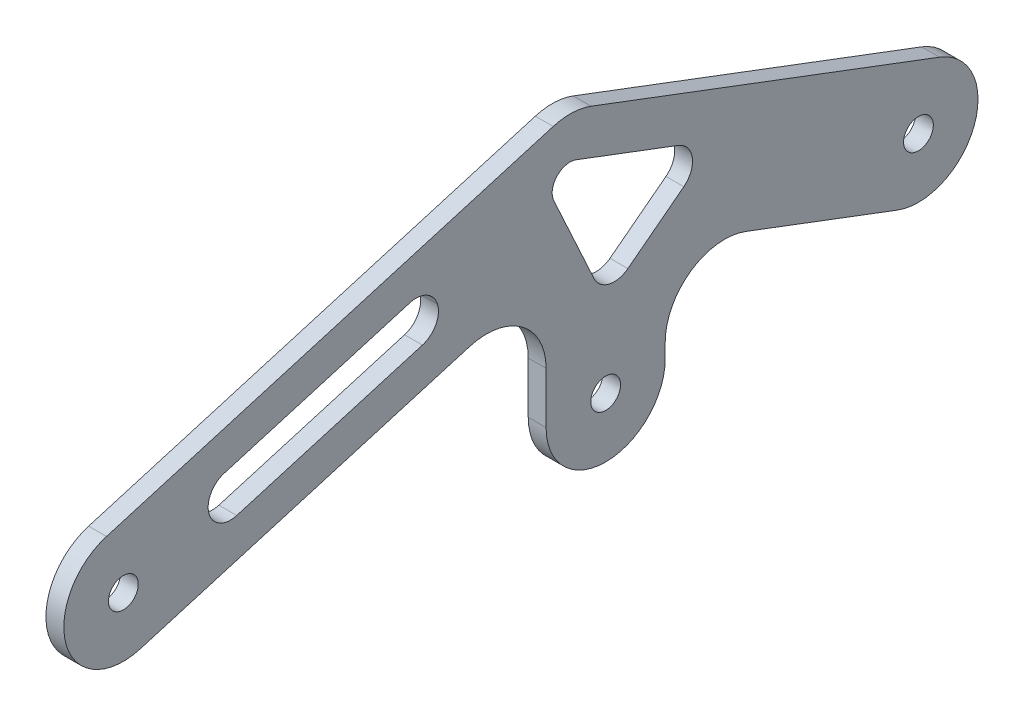
SolidWorks part; units mm, degrees
ref_plane "Front Plane" through (0, 0, 0) normal (0, 0, 1) x (1, 0, 0)
ref_plane "Top Plane" through (0, 0, 0) normal (0, 1, 0) x (1, 0, 0)
ref_plane "Right Plane" through (0, 0, 0) normal (1, 0, 0) x (0, 0, -1)
sketch "Sketch4" plane through (0, 0, 0) normal (1, 0, 0) x (0, 0, -1)
  line L0 (92.5, 20) -> (153.5, 20) construction
  line L1 (0, 0) -> (153.5, 0) construction
  line L2 (0, 0) -> (0, 20) construction
  line L3 (0, 20) -> (77.5, 20) construction
  line L4 (153.5, 0) -> (153.5, 20) construction
  line L6 (77.5, 20) -> (77.5, 39.6162) construction
  line L7 (77.5, 39.6162) -> (92.5, 39.6162) construction
  line L8 (92.5, 20) -> (92.5, 39.6162) construction
  circle A0 centre (10, 10) radius 2.5 construction
  circle A1 centre (143.5, 10) radius 2.5 construction
  circle A2 centre (85, 32.1162) radius 3 construction
  dimension "D2" = 5
  dimension "D3" = 5
  dimension "D4" = 133.5
  dimension "D5" = 10
  dimension "D7" = 10
  dimension "D8" = 10
  dimension "D10" = 6
  dimension "D12" = 7.5
  dimension "D13" = 22.1162
  dimension "D14" = 75
  dimension "D1" = 20
  dimension "D6" = 10
  dimension "D9" = 15
  dimension "D11" = 7.5
sketch "Sketch3" plane through (0, 0, 0) normal (1, 0, 0) x (0, 0, -1)
  line L14 (7.1716, 19.5917) -> (82.1716, 41.7079)
  line L18 (12.8284, 0.4083) -> (80.9802, 20.5051)
  line L22 (100.9802, 15.384) -> (139.9637, 0.6461)
  line L23 (147.0363, 19.3539) -> (88.5363, 41.4701)
  line L25 (80.9802, 20.5051) -> (80.9802, -1.4935)
  line L26 (100.9802, 15.384) -> (100.9802, -1.4935)
  circle A2 centre (85, 32.1162) radius 3
  arc A3 (7.1716, 19.5917) -> (12.8284, 0.4083) centre (10, 10) ccw
  arc A6 (88.5363, 41.4701) -> (82.1716, 41.7079) centre (85, 32.1162) ccw
  arc A7 (139.9637, 0.6461) -> (147.0363, 19.3539) centre (143.5, 10) ccw
  arc A8 (80.9802, -1.4935) -> (100.9802, -1.4935) centre (90.9802, -1.4935) ccw
  circle A9 centre (90.9802, -1.4935) radius 2.5
  circle A10 centre (10, 10) radius 2.5
  circle A12 centre (143.5, 10) radius 2.5
  dimension "D4" = 20
  dimension "D5" = 20
  dimension "D7" = 33.6097
  dimension "D8" = 5.9802
  dimension "D10" = 5
  dimension "D9" = 5
  dimension "D6" = 20
  dimension "D1" = 20
  dimension "D11" = 5
extrude "Boss-Extrude2" add sketch "Sketch3" along normal blind 3
fillet "Fillet1" radius 10 2 edges at (1.5, 15.384, -100.9802) (1.5, 20.5051, -80.9802)
ref_plane "Min 34.36" through (0, -31.4884, -7.6473) normal (0, -0.9718, -0.236) x (-1, 0, 0)
ref_plane "Max 141.51" through (0, 61.7296, -103.5497) normal (0, 0.5121, -0.859) x (-1, 0, 0)
ref_plane "Max 18.41" through (0, -68.9516, -79.9112) normal (0, 0.6533, 0.7571) x (-1, 0, 0)
ref_plane "Min 23.86" through (0, 67.8436, -88.3815) normal (0, 0.6089, -0.7932) x (-1, 0, 0)
sketch "Sketch5" plane through (0, 0, 0) normal (1, 0, 0) x (0, 0, -1)
  line L0 (23.3268, 17.8395) -> (61.6935, 29.1532)
  line L1 (61.6935, 29.1532) -> (63.8148, 21.9594)
  line L2 (63.8148, 21.9594) -> (25.4482, 10.6458)
  line L3 (25.4482, 10.6458) -> (23.3268, 17.8395)
  line L5 (82.1716, 41.7079) -> (7.1716, 19.5917) construction
  line L6 (86.0609, 34.9224) -> (109.4455, 26.0817)
  line L7 (109.4455, 26.0817) -> (90.9802, 11.9104)
  line L8 (90.9802, 11.9104) -> (82.2739, 30.864)
  line L9 (147.0363, 19.3539) -> (88.5363, 41.4701) construction
  line L10 (80.9802, 7.1306) -> (80.9802, -1.4935) construction
  circle A1 centre (10, 10) radius 2.5 construction
  circle A2 centre (85, 32.1162) radius 3 construction
  arc A3 (86.0609, 34.9224) -> (82.2739, 30.864) centre (85, 32.1162) ccw
  dimension "D3" = 15
  dimension "D1" = 7.5
  dimension "D2" = 6.25
  dimension "D4" = 40
  dimension "D5" = 10
  dimension "D6" = 25
  dimension "D7" = 18.9535
extrude "Cut-Extrude1" cut sketch "Sketch5" along normal blind 10
fillet "Fillet2" radius 3.75 6 edges at (1.5, 11.9104, -90.9802) (1.5, 26.0817, -109.4455) (1.5, 29.1532, -61.6935) (1.5, 21.9594, -63.8148) (1.5, 10.6458, -25.4482) (1.5, 17.8395, -23.3268)
